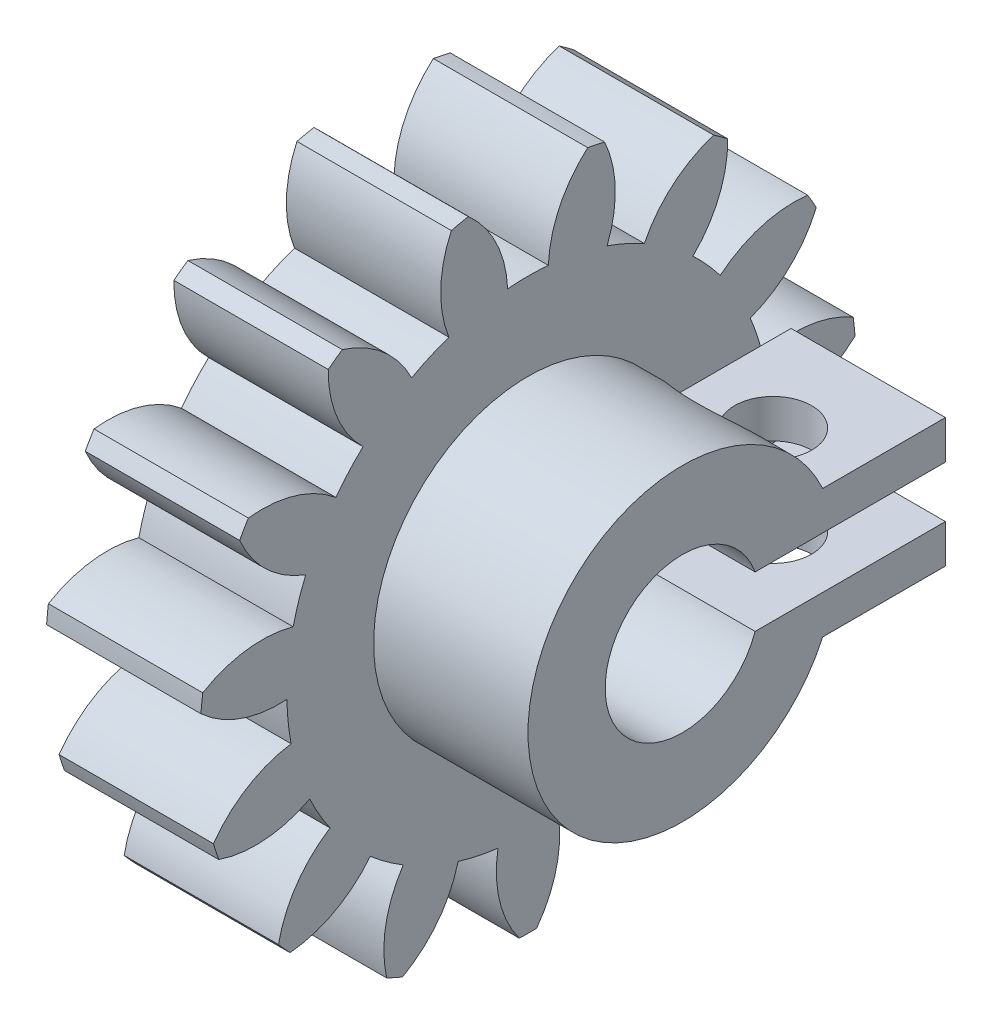
SolidWorks part; units mm, degrees
ref_plane "Plane1" through (0, 0, 0) normal (0, 0, 1) x (1, 0, 0)
ref_plane "Plane2" through (0, 0, 0) normal (0, 1, 0) x (1, 0, 0)
ref_plane "Plane3" through (0, 0, 0) normal (1, 0, 0) x (0, 0, -1)
sketch "HoldingSke" plane through (0, 0, 0) normal (0, 1, 0) x (1, 0, 0)
  line L0 (0, 0) -> (0.644, -0.1725)
  line L1 (-15, 0) -> (100, 0) construction
  line L2 (0, 0) -> (-2.1039, 2.3779)
  line L3 (0, 0) -> (-11.863, 4.5341)
  line L4 (0, 0) -> (8.3417, 2.2352)
  line L5 (0, 0) -> (-46.8476, -17.4728)
  line L6 (0, 0) -> (-4.9738, -3.3558)
  line L7 (-2.1039, 2.3779) -> (8.6586, 51.2059)
  line L8 (-76.2, 54.61) -> (-75.2, 54.61)
  line L9 (-71.009, 38.7566) -> (-53.1078, 45.2721)
  line L10 (-76.2, 71.12) -> (104.1128, 71.12)
  line L11 (0, 0) -> (-6, 0)
  line L12 (-76.2, 101.6) -> (-76.147, 101.6)
  line L13 (24.9733, 27.94) -> (52.9518, 28.4284)
  line L14 (24.9733, 27.94) -> (24.9743, 27.94)
  line L15 (24.9733, 27.94) -> (100.4006, 29.5858)
  line L16 (-63.627, -1.5) -> (-12.827, -1.5)
  circle A0 centre (0, 0) radius 3
  circle A1 centre (0, 0) radius 9.374
  circle A2 centre (0, 0) radius 37.5
  circle A3 centre (0, 0) radius 3
  dimension "Num_teeth" = 15
  dimension "Pitch_radius" = 180.3128
  dimension "Width" = 6
  dimension "Thickness" = 6
sketch "BasProSke" plane through (0, 0, 0) normal (0, 1, 0) x (1, 0, 0)
  line L0 (-10, 0) -> (60, 0) construction
  line L1 (0, 0) -> (0, 12.75)
  line L2 (0, 0) -> (6, 0)
  line L3 (6, 0) -> (6, 12.75)
  line L4 (6, 12.75) -> (0, 12.75)
  dimension "Thickness" = 6
  dimension "Diameter" = 25.5
revolve "Base-Revolve" add sketch "BasProSke" angle 360 about L0
sketch "TooCutSke" plane through (0, 0, 0) normal (1, 0, 0) x (0, 0, -1)
  line L1 (0, 0) -> (0, 107) construction
  line L2 (0, 0) -> (-1.2686, 11.1782) construction
  line L3 (0, 0) -> (-4.6563, 21.9061) construction
  line L4 (-1.2686, 11.1782) -> (-2.3281, 10.953) construction
  arc A0 (0.7915, 9.3405) -> (-0.7915, 9.3405) centre (0, 0) ccw
  arc A1 (2.3447, 12.5584) -> (-2.3447, 12.5584) centre (0, 0) ccw
  circle A2 centre (0, 0) radius 11.25 construction
  circle A3 centre (0, 0) radius 10.5715 construction
  arc A4 (-0.7915, 9.3405) -> (-2.3447, 12.5584) centre (-5.2877, 9.1541) ccw
  arc A5 (2.3447, 12.5584) -> (0.7915, 9.3405) centre (5.2877, 9.1541) ccw
extrude "ToothCut" cut sketch "TooCutSke" along normal through all
fillet "Breaks" [suppressed] radius 0.03 tangent propagation no
fillet "RootFillets" [suppressed] radius 0.376
pattern_circular "TeethCuts" count 15 every 24 about axis through (-10, 0, 0) along (1, 0, 0) of "ToothCut", "RootFillets", "Breaks"
sketch "HubNeaOneSke" plane through (0, 0, 0) normal (-1, 0, 0) x (0, 0, 1)
  circle A0 centre (0, 0) radius 9.374
  dimension "Diameter" = 18.748
extrude "HubNearOne" [suppressed] add sketch "HubNeaOneSke" along normal blind 44.0001
sketch "HubNeaBotSke" plane through (0, 0, 0) normal (-1, 0, 0) x (0, 0, 1)
  circle A0 centre (0, 0) radius 9.374
  dimension "Diameter" = 18.748
extrude "HubNearBoth" [suppressed] add sketch "HubNeaBotSke" along normal blind 22
ref_plane "FarPln" through (6, 0, 0) normal (1, 0, 0) x (0, 0, -1)
sketch "HubFarSke" plane through (6, 0, 0) normal (1, 0, 0) x (0, 0, -1)
  circle A0 centre (0, 0) radius 9.374
  dimension "Diameter" = 18.748
extrude "HubFar" [suppressed] add sketch "HubFarSke" along normal blind 22
sketch "BorSke" plane through (0, 0, 0) normal (1, 0, 0) x (0, 0, -1)
  circle A0 centre (0, 0) radius 3
  dimension "Diameter" = 6
extrude "Bore" cut sketch "BorSke" along normal mid plane 100.0001
sketch "KeySke" plane through (0, 0, 0) normal (1, 0, 0) x (0, 0, -1)
  line L0 (-1, 0) -> (-1, 4)
  line L1 (-1, 4) -> (1, 4)
  line L2 (1, 4) -> (1, 0)
  line L3 (0, 0) -> (0, 34) construction
  line L4 (-1, 0) -> (1, 0)
  dimension "Width" = 2
extrude "Keyway" [suppressed] cut sketch "KeySke" along normal mid plane 100.0001
pattern_circular "Keyway2" [suppressed] count 2 every 90 about axis through (-10, 0, 0) along (1, 0, 0) reverse direction yes
sketch "Sketch1" plane through (6, 0, 0) normal (1, 0, 0) x (0, 0, -1)
  line L0 (-8.9706, 0) -> (4.6808, 0) construction
  circle A0 centre (0, 0) radius 3
  circle A2 centre (0, 0) radius 6
  point P12 (0, 0)
  dimension "D1" = 12
extrude "Boss-Extrude2" add sketch "Sketch1" along normal blind 6
sketch "Sketch2" plane through (12, 0, 0) normal (1, 0, 0) x (0, 0, -1)
  line L1 (1.8125, 1) -> (7.0934, 1)
  line L2 (1.8125, 1) -> (1.8125, -1)
  line L3 (1.8125, -1) -> (7.0934, -1)
  line L4 (7.0934, 1) -> (7.0934, -1)
  line L5 (1.8125, 1) -> (7.0934, -1) construction
  line L6 (1.8125, -1) -> (7.0934, 1) construction
  point P0 (4.453, 0)
  point P5 (4.453, 0)
  dimension "D1" = 2
extrude "Cut-Extrude1" cut sketch "Sketch2" against normal up to surface (6 mm away) up to face at (6, 0, 0)
sketch "Sketch3" plane through (0, -1, 0) normal (0, 1, 0) x (1, 0, 0)
  line L0 (12, 2.8284) -> (12, 5.9161) construction
  line L1 (6, 2.8284) -> (12, 2.8284)
  line L2 (6, 2.8284) -> (6, 10.2244)
  line L3 (6, 10.2244) -> (12, 10.2244)
  line L4 (12, 2.8284) -> (12, 10.2244)
  point P5 (12, 2.8284)
extrude "Boss-Extrude3" add sketch "Sketch3" against normal blind 1.5
sketch "Sketch5" plane through (0, 1, 0) normal (0, -1, 0) x (1, 0, 0)
  line L0 (6, -10.2244) -> (6, -9.3205) construction
  line L1 (6, -2.8284) -> (12, -2.8284) construction
  line L2 (6, -2.8284) -> (6, -9.3205) construction
  line L3 (12, -10.2244) -> (6, -10.2244) construction
  line L4 (12, -2.8284) -> (12, -10.2244) construction
  line L5 (6, -10.2244) -> (6, -9.3205)
  line L6 (6, -2.8284) -> (12, -2.8284)
  line L7 (6, -2.8284) -> (6, -9.3205)
  line L8 (12, -10.2244) -> (6, -10.2244)
  line L9 (12, -2.8284) -> (12, -10.2244)
extrude "Boss-Extrude4" add sketch "Sketch5" against normal blind 1.5
sketch "Sketch6" plane through (0, -1, 0) normal (0, 1, 0) x (1, 0, 0)
  line L0 (12, 2.8284) -> (12, 10.2244) construction
  line L1 (12, 10.2244) -> (6, 10.2244) construction
  circle A0 centre (9, 6.5264) radius 1.5
  point P0 (0, 0)
  point P3 (12, 6.5264)
  point P4 (9.1304, 5.8163)
  point P7 (9, 10.2244)
  dimension "D1" = 3
extrude "Cut-Extrude2" cut sketch "Sketch6" against normal through all both and the other way through all
sketch "Sketch7" plane through (0, 2.5, 0) normal (0, 1, 0) x (1, 0, 0)
  arc A5 (6.9017, 4.3823) -> (11.0983, 4.3823) centre (9, 6.5264) ccw
  arc A6 (11.0983, 4.3823) -> (6.9017, 4.3823) centre (9, 6.5264) ccw
  arc A7 (6.9017, 4.3823) -> (11.0983, 4.3823) centre (9, 6.5264) ccw
  arc A8 (11.0983, 4.3823) -> (6.9017, 4.3823) centre (9, 6.5264) ccw
  dimension "D1" = 1.5
extrude "Cut-Extrude3" cut sketch "Sketch7" along normal through all
equation "' \"Module@HoldingSke\" = 6.35"
equation "' \"Num_teeth@HoldingSke\" = 12"
equation "' \"Ap@HoldingSke\" =  20"
equation "' \"Ap@HoldingSke\" = 20"
equation "' \"Width@HoldingSke\" = 0.5 * 25.4"
equation "' \"Hub_dia@HoldingSke\"= 1 * 25.4"
equation "' \"Hub_dia@HoldingSke\" = 1 * 25.4"
equation "' \"Overall_len@HoldingSke\" = 1.0 * 25.4"
equation "' \"Bore@HoldingSke\" = 0.75 * 25.4"
equation "' \"T_dim@HoldingSke\" = 0.1 * 25.4"
equation "' \"Width@KeySke\" = 0.25 * 25.4"
equation "' \"Show_teeth@HoldingSke\" = 13"
equation "' \"Backlash@HoldingSke\" = 0.009 * 25.4"
equation "' \"Addendum_fac@HoldingSke\" = 1.0"
equation "' \"Dedendum_fac@HoldingSke\" = 1.25"
equation "' \"Dedendum_add@HoldingSke\" = 0.00005 * 25.4"
equation "' \"Clearance_fac@HoldingSke\" = 0.25"
equation "\"Pitch@HoldingSke\" = 1 / \"Module@HoldingSke\""
equation "\"Overcut_dia@TooCutSke\" = (\"Num_teeth@HoldingSke\" + 2 * \"Addendum_fac@HoldingSke\") / \"Pitch@HoldingSke\" + 0.002 * 25.4"
equation "\"Pitch_dia@TooCutSke\" = \"Num_teeth@HoldingSke\" / \"Pitch@HoldingSke\""
equation "\"Base_dia@TooCutSke\" = \"Num_teeth@HoldingSke\" / \"Pitch@HoldingSke\" * cos((\"Ap@HoldingSke\"  * 3.14159265 / 180))"
equation "\"Root_dia@TooCutSke\" = (\"Num_teeth@HoldingSke\" + 2) / \"Pitch@HoldingSke\" - 2 * (\"Addendum_fac@HoldingSke\" + \"Dedendum_fac@HoldingSke\") / \"Pitch@HoldingSke\" - \"Dedendum_add@HoldingSke\" * 2"
equation "\"Half_ang@TooCutSke\" = 180 / \"Num_teeth@HoldingSke\""
equation "\"Half_CT@TooCutSke\" = \"Num_teeth@HoldingSke\" / \"Pitch@HoldingSke\" * sin((3.14159265 / 2 / \"Num_teeth@HoldingSke\")) / 2 - 7 * \"Backlash@HoldingSke\" / 4"
equation "\"Flank_rad@TooCutSke\" = \"Num_teeth@HoldingSke\" / \"Pitch@HoldingSke\" / 5"
equation "\"Radius@RootFillets\" = \"Clearance_fac@HoldingSke\" / \"Pitch@HoldingSke\" + \"Dedendum_add@HoldingSke\""
equation "\"Break_rad@Breaks\" = 0.02 / \"Pitch@HoldingSke\""
equation "\"Thickness@HoldingSke\" = \"Width@HoldingSke\""
equation "\"OAL@HoldingSke\" = \"Thickness@HoldingSke\""
equation "\"MHD@HoldingSke\" = (\"Num_teeth@HoldingSke\" + 2) / \"Pitch@HoldingSke\" - 2 * (\"Addendum_fac@HoldingSke\" + \"Dedendum_fac@HoldingSke\")  / \"Pitch@HoldingSke\" - \"Dedendum_add@HoldingSke\" * 2"
equation "\"MBD@HoldingSke\" = (\"Num_teeth@HoldingSke\" + 2) / \"Pitch@HoldingSke\" - 2 * (\"Addendum_fac@HoldingSke\" + \"Dedendum_fac@HoldingSke\")  / \"Pitch@HoldingSke\" - \"Dedendum_add@HoldingSke\" * 2 - 0.002 * 25.4"
equation "\"MHD@HoldingSke\" = ((sgn( \"MHD@HoldingSke\" - \"Hub_dia@HoldingSke\" )-1)*( \"MHD@HoldingSke\" - \"Hub_dia@HoldingSke\" ))/-2+ \"Hub_dia@HoldingSke\""
equation "\"MBD@HoldingSke\" = ((sgn( \"MBD@HoldingSke\" - \"Bore@HoldingSke\" )-1)*( \"MBD@HoldingSke\" - \"Bore@HoldingSke\" ))/-2+ \"Bore@HoldingSke\""
equation "\"OAL@HoldingSke\" = ((sgn( \"OAL@HoldingSke\" - \"Overall_len@HoldingSke\" )+1)*( \"OAL@HoldingSke\" - \"Overall_len@HoldingSke\" ))/2 + \"Overall_len@HoldingSke\" + 0.000002 * 25.4"
equation "\"Num_teeth@TeethCuts\" = int( \"Show_teeth@HoldingSke\" ) + 1"
equation "\"Num_teeth@TeethCuts\" = ((sgn( \"Num_teeth@TeethCuts\" - \"Num_teeth@HoldingSke\" )-1)*( \"Num_teeth@TeethCuts\" - \"Num_teeth@HoldingSke\" ))/-2+ \"Num_teeth@HoldingSke\""
equation "\"Num_teeth@TeethCuts\" = ((sgn( \"Num_teeth@TeethCuts\" - 2.0)+1)*( \"Num_teeth@TeethCuts\" - 2.0))/2 +2.0"
equation "\"Angle@TeethCuts\" = 360.0 / \"Num_teeth@HoldingSke\""
equation "\"Diameter@BasProSke\" = (\"Num_teeth@HoldingSke\" + 2 * \"Addendum_fac@HoldingSke\") / \"Pitch@HoldingSke\""
equation "\"Thickness@BasProSke\"  = \"Thickness@HoldingSke\""
equation "' \"Fillet_rad@BasProSke\" =  \"Thickness@HoldingSke\" * 0.05"
equation "' \"Fillet_rad@BasProSke\" = \"Thickness@HoldingSke\" * 0.05"
equation "\"MHD@HoldingSke\" = ((sgn( \"MHD@HoldingSke\" - \"Root_dia@TooCutSke\" )-1)*( \"MHD@HoldingSke\" - \"Root_dia@TooCutSke\" ))/-2+ \"Root_dia@TooCutSke\""
equation "\"Diameter@HubNeaOneSke\" = \"MHD@HoldingSke\""
equation "\"Length@HubNearOne\" = \"OAL@HoldingSke\" - \"Thickness@BasProSke\""
equation "\"Diameter@HubNeaBotSke\" = \"MHD@HoldingSke\""
equation "\"Length@HubNearBoth\" = ( \"OAL@HoldingSke\" - \"Thickness@BasProSke\" ) / 2.0"
equation "\"Thickness@FarPln\" = \"Thickness@BasProSke\""
equation "\"Diameter@HubFarSke\" = \"MHD@HoldingSke\""
equation "\"Length@HubFar\" = ( \"OAL@HoldingSke\" - \"Thickness@BasProSke\" ) / 2.0"
equation "\"Diameter@BorSke\" = \"MBD@HoldingSke\""
equation "\"D1@Bore\" = \"OAL@HoldingSke\" * 2.0"
equation "\"D1@Keyway\" = \"OAL@HoldingSke\" * 2.0"
equation "\"Offset@KeySke\" = \"T_dim@HoldingSke\" + \"MBD@HoldingSke\" / 2.0"
